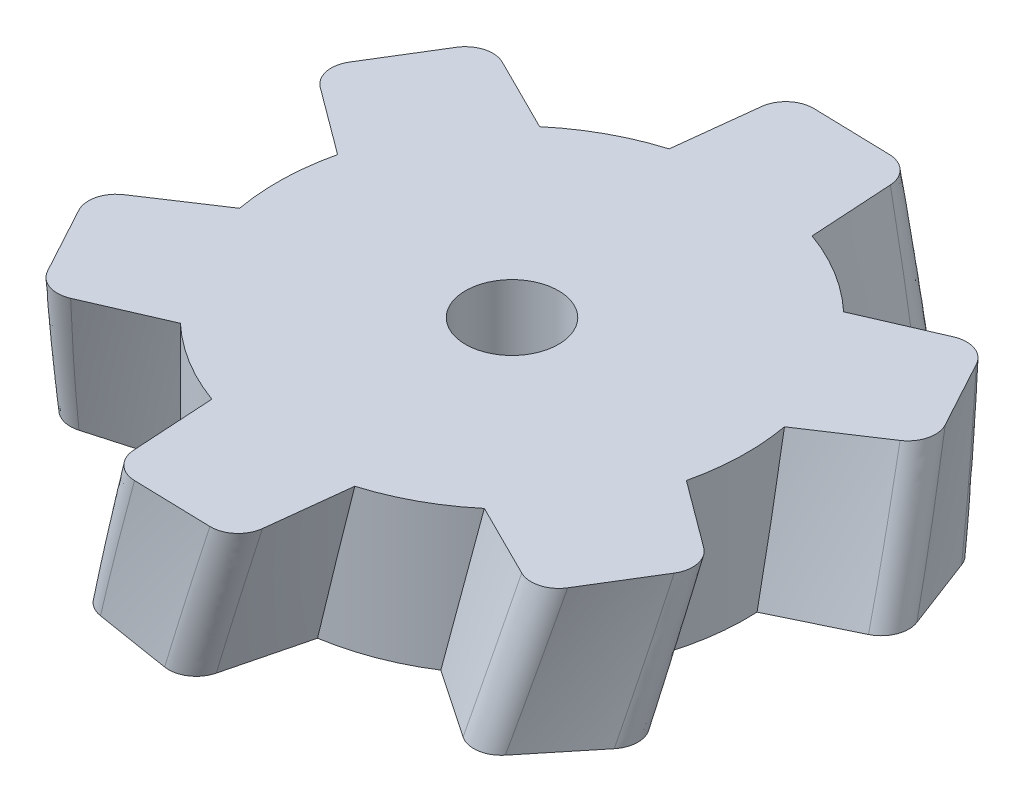
SolidWorks part; units mm, degrees
ref_plane "Front Plane" through (0, 0, 0) normal (0, 0, 1) x (1, 0, 0)
ref_plane "Top Plane" through (0, 0, 0) normal (0, 1, 0) x (1, 0, 0)
ref_plane "Right Plane" through (0, 0, 0) normal (1, 0, 0) x (0, 0, -1)
sketch "Sketch1" plane through (0, 0, 0) normal (0, 1, 0) x (1, 0, 0)
  circle A0 centre (0, 0) radius 8.509
  dimension "D1" = 17.018
extrude "Boss-Extrude1" add sketch "Sketch1" along normal blind 5.2
sketch "Sketch2" plane through (0, 5.2, 0) normal (0, 1, 0) x (1, 0, 0)
  circle A0 centre (0, 0) radius 1.6875
  dimension "D1" = 3.375
extrude "Cut-Extrude1" cut sketch "Sketch2" against normal through all
sketch "Sketch3" plane through (0, 5.2, 0) normal (0, 1, 0) x (1, 0, 0)
  line L0 (0, 0) -> (0.3304, 12.3503) construction
  line L1 (-1.0829, 12.0423) -> (1.7251, 11.9672)
  line L2 (-3.5854, 8.6079) -> (4.8903, 8.3812) construction
  line L3 (-2.1031, 11.1564) -> (-2.5728, 7.0545)
  line L4 (2.6965, 11.028) -> (2.9463, 6.9068)
  circle A0 centre (0, 0) radius 8.509 construction
  arc A1 (-2.1031, 11.1564) -> (-1.0829, 12.0423) centre (-1.1096, 11.0426) cw
  arc A2 (2.6965, 11.028) -> (1.7251, 11.9672) centre (1.6984, 10.9675) ccw
  arc A4 (2.9463, 6.9068) -> (-2.5728, 7.0545) centre (0, 0) ccw
  point P10 (-2.4474, 8.1494)
  point P12 (-1.9989, 12.0668)
  point P14 (2.8796, 8.0069)
  point P17 (0.3211, 12.0047)
  dimension "D4" = 1
  dimension "D1" = 3.5
  dimension "D2" = 2.32
  dimension "D3" = 95
sketch "Sketch4" plane through (0, 5.2, 0) normal (0, 1, 0) x (1, 0, 0)
  circle A0 centre (0, 0) radius 8.509 construction
  circle A1 centre (0, 0) radius 8.509
curve "Helix/Spiral1" pitch 246.13 height 7.55 radius 8.509 centre (0, 5.2, 0) axis (0, -1, 0) start towards (0, 0, 1)
sweep "Sweep1" add profiles "Sketch3" path "Helix/Spiral1"
pattern_circular "CirPattern1" count 6 over 360 about axis through (0, 5.2, 0) along (0, -1, 0) of "Sweep1"
sketch "Sketch5" plane through (0, 0, 0) normal (0, -1, 0) x (1, 0, 0)
  circle A0 centre (0, 0) radius 14.9643
extrude "Cut-Extrude3" cut sketch "Sketch5" along normal blind 5
